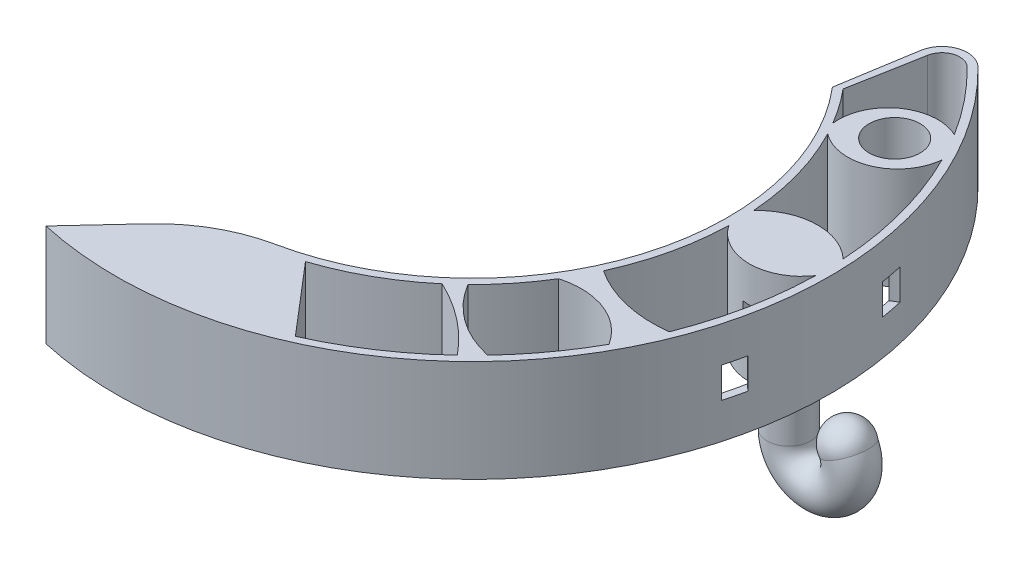
SolidWorks part; units mm, degrees
ref_plane "Front Plane" through (0, 0, 0) normal (0, 0, 1) x (1, 0, 0)
ref_plane "Top Plane" through (0, 0, 0) normal (0, 1, 0) x (1, 0, 0)
ref_plane "Right Plane" through (0, 0, 0) normal (1, 0, 0) x (0, 0, -1)
sketch "Sketch1" plane through (0, 0, 0) normal (0, 1, 0) x (1, 0, 0)
  line L0 (25.4386, 21.5353) -> (27.9933, 37.33)
  line L2 (1.1109, -33.3115) -> (-10.2169, -45.5277)
  arc A0 (25.4386, 21.5353) -> (1.1109, -33.3115) centre (0, 0) cw
  arc A1 (27.9933, 37.33) -> (-10.2169, -45.5277) centre (0, 0) cw
  dimension "D1" = 33.33
  dimension "D6" = 46.66
  dimension "D2" = 16
  dimension "D3" = 37.33
  dimension "D4" = 60
  dimension "D5" = 16.66
extrude "Boss-Extrude1" add sketch "Sketch1" along normal blind 13.33
fillet "Fillet1" radius 20 1 edges at (1.1109, 6.665, 33.3115)
sketch "Sketch2" plane through (0, 13.33, 0) normal (0, 1, 0) x (1, 0, 0)
  line L0 (-3.8058, -38.6138) -> (-3.8058, -39.2805)
  line L1 (-3.8058, -39.2805) -> (-4.4705, -39.3307)
  line L2 (-3.8058, -38.6138) -> (-10.2169, -45.5277) construction
  line L3 (-3.8058, -39.2805) -> (-4.1382, -38.9722) construction
  line L4 (-4.4705, -39.3307) -> (-3.8058, -38.6138)
  dimension "D1" = 0.6667
  dimension "D2" = 0.4533
extrude "Cut-Extrude1" [suppressed] cut sketch "Sketch2" against normal through all and the other way through all
pattern_linear "LPattern1" [suppressed] count 7 spacing 1.33 of bodies 102
sketch "Sketch3" plane through (0, 13.33, 0) normal (0, 1, 0) x (1, 0, 0)
  line L0 (29.1016, 16.2476) -> (40.6522, 22.9032) construction
  circle A0 centre (35.2891, 19.8129) radius 3.33
  arc A1 (6.787, -32.6317) -> (25.4386, 21.5353) centre (0, 0) ccw construction
  arc A2 (-10.2169, -45.5277) -> (27.9933, 37.33) centre (0, 0) ccw construction
  dimension "D1" = 6.66
  dimension "D2" = 10
extrude "Cut-Extrude2" cut sketch "Sketch3" against normal through all
fillet "Fillet2" radius 3.333 1 edges at (27.9933, 6.665, -37.33)
sketch "Sketch4" plane through (0, 13.33, 0) normal (0, 1, 0) x (1, 0, 0)
  circle A0 centre (40.567, 0.7155) radius 2.8333
  circle A1 centre (35.2891, 19.8129) radius 3.33 construction
  dimension "D1" = 5.6667
  dimension "D2" = 19.8133
  dimension "D3" = 40.5733
sketch "Sketch6" plane through (0, 0, 0) normal (0, 0, 1) x (1, 0, 0)
  line L0 (40.567, 13.33) -> (40.567, 20.6367)
  line L1 (43.4004, 13.33) -> (37.7337, 13.33) construction
  arc A0 (40.567, 20.6367) -> (48.3846, 18.9381) centre (44.6604, 20.6367) cw
  dimension "D2" = 8
  dimension "D1" = 4.0933
  dimension "D3" = 7.3067
sweep "Sweep1" add profiles "Sketch4" path "Sketch6"
dome "Dome1" faces to dome 1 distance 3.3333 reverse direction no elliptical dome no face at (48.3846, 18.9381, 2.1178) parameters "D1"=3.3333
ref_plane "Plane1" through (0, 6.665, 0) normal (0, 1, 0) x (1, 0, 0)
sketch "Sketch7" plane through (0, 6.665, 0) normal (0, 1, 0) x (1, 0, 0)
  arc A0 (44.9659, -12.459) -> (45.646, -9.6747) centre (0, 0) ccw
  arc A1 (-10.2169, -45.5277) -> (32.6689, 33.3151) centre (0, 0) ccw construction
  arc A2 (46.0579, 7.4718) -> (45.5122, 10.2856) centre (0, 0) ccw
  arc A3 (45.646, -9.6747) -> (46.0579, 7.4718) centre (52.1921, -1.2537) cw
  arc A4 (44.9659, -12.459) -> (45.5122, 10.2856) centre (52.1921, -1.2537) cw
  circle A5 centre (35.2891, 19.8129) radius 3.33 construction
  dimension "D1" = 10.666
  dimension "D2" = 13.3333
  dimension "D3" = 2.8667
  dimension "D4" = 21.0667
extrude "Cut-Extrude3" cut sketch "Sketch7" against normal mid plane 4
ref_plane "Plane3" through (-10.2169, 0, 45.5277) normal (-0.219, 0, 0.9757) x (0.9757, 0, 0.219)
sketch "Sketch10" plane through (0, 0, 0) normal (0, -1, 0) x (1, 0, 0)
  line L2 (-2.2542, 38.9234) -> (-9.2389, 45.7362)
  line L3 (-9.2389, 45.7362) -> (-10.2169, 45.5277)
  line L4 (6.787, 32.6317) -> (7.4727, 33.8523)
  line L5 (-9.2389, 45.7362) -> (17.4523, 45.7362) construction
  line L6 (7.4727, 33.8523) -> (-3.2128, 33.8523) construction
  line L22 (25.4386, -21.5353) -> (27.0451, -31.4676)
  line L23 (-10.2169, 45.5277) -> (-3.8058, 38.6138)
  line L45 (-10.2169, 45.5277) -> (-3.8058, 38.6138)
  arc A1 (32.6689, -33.3151) -> (-10.2169, 45.5277) centre (0, 0) ccw construction
  arc A2 (-3.8058, 38.6138) -> (6.787, 32.6317) centre (10.8595, 52.2126) ccw
  arc A3 (-2.2542, 38.9234) -> (7.4727, 33.8523) centre (10.8595, 52.2126) ccw
  arc A4 (27.0451, -31.4676) -> (32.6689, -33.3151) centre (30.3353, -30.9354) ccw
  arc A5 (32.6689, -33.3151) -> (-10.2169, 45.5277) centre (0, 0) ccw
  arc A6 (-3.8058, 38.6138) -> (6.787, 32.6317) centre (10.8595, 52.2126) ccw
  arc A7 (25.4386, -21.5353) -> (6.787, 32.6317) centre (0, 0) ccw
  dimension "D2" = 20
  dimension "D4" = 18.6701
  dimension "D3" = 1.4
  dimension "D5" = 9.757
  dimension "D6" = 1
  dimension "D7" = 44.286
  dimension "D11" = 1.5821
  dimension "D12" = 60.674
  dimension "D13" = 192.034
  dimension "D1" = 0
sketch "Sketch11" plane through (-10.2169, 0, 45.5277) normal (-0.219, 0, 0.9757) x (0.9757, 0, 0.219)
  line L0 (0, 0) -> (-0.144, -4.5)
  arc A0 (-0.144, -4.5) -> (-7.0098, -18.952) centre (-20.1338, -3.8603) cw
  dimension "D1" = 20
  dimension "D2" = 4.5
  dimension "D3" = 16
sweep "Sweep3" [suppressed] add profiles "Sketch10" path "Sketch11"
fillet "Fillet3" [suppressed] radius 3.3333
sketch "Sketch8" plane through (0, 0, 0) normal (0, -1, 0) x (1, 0, 0)
  arc A0 (22.7195, 25.9629) -> (4.3537, 34.2242) centre (0, 0) ccw
  arc A1 (25.3537, 28.9731) -> (-1.2031, 38.4812) centre (0, 0) ccw
  arc A2 (4.3537, 34.2242) -> (-1.2031, 38.4812) centre (7.3628, 43.9074) cw
  arc A3 (25.3537, 28.9731) -> (22.7195, 25.9629) centre (21.9954, 29.2542) cw
  dimension "D1" = 34.5
  dimension "D2" = 38.5
  dimension "D3" = 10.14
  dimension "D4" = 3.37
  dimension "D7" = 21
  dimension "D5" = 4
  dimension "D6" = 7
  dimension "D8" = 27
mirror "Mirror1" [suppressed] about plane through (0, 6.665, 0) normal (0, 1, 0)
sketch "Sketch15" [suppressed] plane through (0, 0, 0) normal (1, 0, 0) x (0, 0, -1)
  line L0 (-44.1567, 13.33) -> (-35.6752, 24.018)
rib "Rib2" [suppressed] sketch "Sketch15" sketch "Sketch15" thickness 3 extrusion direction parallel to sketch draft on no parameters "D1"=3
mirror "Mirror2" [suppressed] about plane through (0, 6.665, 0) normal (0, 1, 0)
fillet "Fillet6" [suppressed] radius 2
fillet "Fillet7" [suppressed] radius 2
fillet "Fillet9" [suppressed] radius 2
mirror "Mirror3" about plane through (0, 6.665, 0) normal (0, 1, 0) of "Dome1", "Sweep1"
sketch "Sketch16" plane through (0, 13.33, 0) normal (0, 1, 0) x (1, 0, 0)
  line L1 (60.3185, -9.5057) -> (23.5897, -9.5057)
  line L2 (60.3185, -9.5057) -> (60.3185, 9.5057)
  line L3 (60.3185, 9.5057) -> (23.5897, 9.5057)
  line L4 (23.5897, -9.5057) -> (23.5897, 9.5057)
  line L5 (60.3185, -9.5057) -> (23.5897, 9.5057) construction
  line L6 (60.3185, 9.5057) -> (23.5897, -9.5057) construction
  point P0 (41.9541, 0)
extrude "Cut-Extrude4" cut sketch "Sketch16" along normal blind 30
sketch "Sketch17" [suppressed] plane through (-9.7279, -0.016, 45.6319) normal (-0.2085, -0.0003, 0.978) x (0.978, -0.0001, 0.2085)
  line L0 (-0.5, 0.016) -> (-0.6437, -4.484) construction
  line L1 (-0.501, 13.346) -> (-0.5, 0.016) construction
  line L2 (-0.501, 13.346) -> (-0.6453, 17.846) construction
  line L3 (-0.5, 0.016) -> (-0.6437, -4.484)
  line L4 (-0.501, 13.346) -> (-0.5, 0.016)
  line L5 (-0.501, 13.346) -> (-0.6453, 17.846)
  line L6 (-7.5117, 32.2975) -> (-7.508, -18.9366)
  ellipse E0 centre (-20.6323, -3.8459) end of major axis (-21.2705, -23.8357) minor radius 19.9989 (-7.508, -18.9366) -> (-0.6437, -4.484) ccw construction
  ellipse E1 centre (-20.6339, 17.2047) end of major axis (-21.2721, -2.7851) minor radius 19.9989 (-0.6453, 17.846) -> (-7.5117, 32.2975) ccw construction
  ellipse E2 centre (-20.6323, -3.8459) end of major axis (-21.2705, -23.8357) minor radius 19.9989 (-7.508, -18.9366) -> (-0.6437, -4.484) ccw
  ellipse E3 centre (-20.6339, 17.2047) end of major axis (-19.9957, 37.1945) minor radius 19.9989 (-0.6453, 17.846) -> (-7.5117, 32.2975) ccw
extrude "Boss-Extrude2" [suppressed] add sketch "Sketch17" along normal blind 1 separate body
ref_axis "Axis1" [suppressed] through (21.9954, 0, 29.2542) along (0, -1, 0)
ref_plane "Plane2" [suppressed] through (8.1155, 0, -3.4448) normal (-0.9205, 0, 0.3907) x (0, -1, 0)
sketch "Sketch18" plane through (0, 0, 0) normal (0, -1, 0) x (1, 0, 0)
  line L0 (28.0391, -31.3529) -> (26.3411, -22.0158)
  line L1 (18.5503, 41.722) -> (10.7491, 32.6038)
  arc A0 (32.0149, -32.5559) -> (38.7606, -24.134) centre (0, 0) ccw
  arc A1 (26.3411, -22.0158) -> (29.5437, -17.4848) centre (0, 0) ccw
  arc A2 (32.0149, -32.5559) -> (28.0391, -31.3529) centre (30.3353, -30.9354) cw
  arc A3 (32.6689, -33.3151) -> (-10.2169, 45.5277) centre (0, 0) ccw construction
  arc A4 (25.4386, -21.5353) -> (6.787, 32.6317) centre (0, 0) ccw construction
  arc A5 (38.7606, -24.134) -> (29.5437, -17.4848) centre (35.9985, -18.2501) cw
  arc A6 (40.8206, -20.4576) -> (30.3945, -15.96) centre (34.354, -21.1149) ccw
  arc A7 (40.8206, -20.4576) -> (45.5738, -2.8036) centre (0, 0) ccw
  arc A8 (30.3945, -15.96) -> (34.2425, -2.4493) centre (0, 0) ccw
  arc A9 (45.5738, -2.8036) -> (34.2425, -2.4493) centre (40.0853, 3.0392) cw
  arc A10 (45.6516, 0.8763) -> (34.3188, 0.8763) centre (39.9852, -2.9825) ccw
  arc A11 (45.6516, 0.8763) -> (42.4626, 16.7859) centre (0, 0) ccw
  arc A12 (34.3188, 0.8763) -> (31.261, 14.188) centre (0, 0) ccw
  arc A13 (42.4626, 16.7859) -> (31.261, 14.188) centre (40.339, 0.4943) ccw
  arc A14 (39.9311, 22.1438) -> (29.2241, 18.014) centre (31.8168, 27.2364) cw
  arc A15 (39.9311, 22.1438) -> (33.2447, 31.299) centre (0, 0) ccw
  arc A16 (29.2241, 18.014) -> (23.9606, 24.5853) centre (0, 0) ccw
  arc A17 (23.9606, 24.5853) -> (33.2447, 31.299) centre (36.2392, 17.3819) cw
  arc A18 (31.261, 33.2804) -> (22.1886, 26.1957) centre (11.2277, 49.5831) cw
  arc A19 (31.261, 33.2804) -> (18.5503, 41.722) centre (0, 0) ccw
  arc A20 (22.1886, 26.1957) -> (10.7491, 32.6038) centre (0, 0) ccw
  dimension "D1" = 1
  dimension "D2" = 1
  dimension "D4" = 6.5
  dimension "D3" = 6.5
  dimension "D8" = 9.58
  dimension "D5" = 26
  dimension "D6" = 31
  dimension "D7" = 12
extrude "Cut-Extrude5" cut sketch "Sketch18" against normal through all
ref_plane "Plane4" through (15.6134, 0, 27.6471) normal (0.4917, 0, 0.8707) x (0.8707, 0, -0.4917)
sketch "Sketch19" plane through (15.6134, 0, 27.6471) normal (0.4917, 0, 0.8707) x (0.8707, 0, -0.4917)
  line L0 (-10.1366, 0) -> (-10.1366, 13.33) construction
  line L1 (-22.3018, 0) -> (-10.1366, 0) construction
  circle A0 centre (-14.1366, 6.665) radius 1.425
  dimension "D2" = 2.85
  dimension "D1" = 4
  dimension "D3" = 6.665
extrude "Cut-Extrude6" cut sketch "Sketch19" along normal mid plane 17.2
